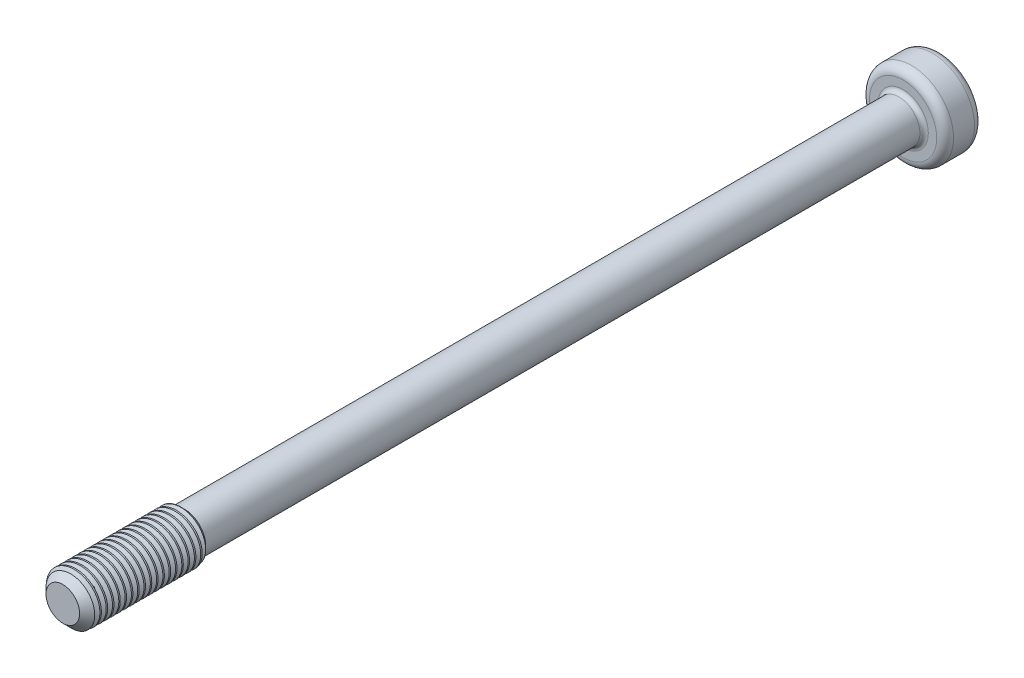
SolidWorks part; units mm, degrees
material "Plain Carbon Steel"
ref_plane "Front Plane" through (0, 0, 0) normal (0, 0, 1) x (1, 0, 0)
ref_plane "Top Plane" through (0, 0, 0) normal (0, 1, 0) x (1, 0, 0)
ref_plane "Right Plane" through (0, 0, 0) normal (1, 0, 0) x (0, 0, -1)
sketch "Sketch1" plane through (0, 0, 0) normal (0, 0, 1) x (1, 0, 0)
  circle A0 centre (0, 0) radius 1
  dimension "D1" = 2
extrude "Boss-Extrude1" add sketch "Sketch1" along normal blind 0.9
sketch "Sketch2" plane through (0, 0, 0.9) normal (0, 0, 1) x (1, 0, 0)
  circle A0 centre (0, 0) radius 0.5
  dimension "D1" = 1
extrude "Boss-Extrude2" add sketch "Sketch2" along normal blind 20
sketch "Sketch4" plane through (0, 0, 0) normal (0, 1, 0) x (1, 0, 0)
  line L0 (-1, -0.9) -> (1, -0.9) construction
  line L1 (-1, -0.9) -> (1, -0.9) construction
  line L2 (1, 0) -> (-1, 0) construction
  line L3 (0, -0.8) -> (0, 0)
  line L4 (1, 0) -> (-1, 0) construction
  line L6 (-0.75, 0) -> (-0.6089, -0.8)
  line L7 (-0.6089, -0.8) -> (0, -0.8)
  line L10 (-0.75, 0) -> (0, 0)
  point P6 (0.0056, -0.8)
  dimension "D1" = 0.25
  dimension "D2" = 0.1
  dimension "D4" = 100
ref_axis "Axis1" through (0, 0, 23.484) along (0, 0, -1)
extrude "Cut-Extrude5" cut sketch "Sketch4" against normal mid plane 0.3 contours L7 L10 L6 | L10 region at (-0.341, 0, 0.3862)
pattern_circular "CirPattern2" count 4 over 360 about axis through (0, 0, 23.484) along (0, 0, -1) of "Cut-Extrude5"
ref_plane "Plane1" through (0, 0, 0) normal (-0.7071, -0.7071, 0) x (0, 0, 1)
sketch "Sketch7" plane through (0, 0, 0) normal (-0.7071, -0.7071, 0) x (0, 0, 1)
  line L0 (0.8, 0.2121) -> (0, 0.2121) construction
  line L1 (0.8, 0.2121) -> (0, 0.2121) construction
  line L2 (0.9, -1) -> (0.9, 1) construction
  line L3 (23.484, 0) -> (-3.7079, 0) construction
  line L4 (0.8, 0) -> (0.9, 0)
  line L5 (0.9, 0) -> (0.8, 0.2121)
  line L6 (0.8, 0.2121) -> (0, 0.3)
  line L7 (0, 0.3) -> (0, 0)
  line L8 (0.8, 0) -> (0, 0)
  point P9 (0.7668, 0.2121)
  point P11 (0.738, 0.2121)
  point P12 (0, 0)
  point P13 (0, 0)
  point P14 (0, 0)
  point P15 (0, 0)
  point P18 (0, 0)
  dimension "D1" = 0.1
  dimension "D2" = 0.3
revolve "Cut-Revolve3" cut sketch "Sketch7" angle 360 about axis through (0, 0, 23.484) along (0, 0, -1) region at (-0.0735, 0.0735, 0.4255) region at (-0.1707, 0.1707, 0.2667)
fillet "Fillet2" radius 0.1 1 edges at (0.5, 0, 0.9)
fillet "Fillet3" radius 0.2 2 edges at (1, 0, 0) (1, 0, 0.9)
sketch "Sketch10" plane through (0, 0, 20.9) normal (0, 0, 1) x (1, 0, 0)
  circle A0 centre (0, 0) radius 0.6
  dimension "D1" = 1.2
extrude "Boss-Extrude3" add sketch "Sketch10" against normal blind 3
sketch "Sketch11" plane through (0, 0, 20.9) normal (0, 0, 1) x (1, 0, 0)
  circle A0 centre (0, 0) radius 0.5
  dimension "D1" = 1
curve "Helix/Spiral1" pitch 0.15 height 3.3 radius 0.5 centre (0, 0, 20.9) axis (0, 0, -1) start towards (-1, 0, 0)
chamfer "Chamfer1" distance 0.2 angle 45 2 edges at (0.6, 0, 17.9) (0.6, 0, 20.9)
sketch "Sketch13" plane through (0, 0, 0) normal (0, 1, 0) x (1, 0, 0)
  line L0 (-0.6, -18.1) -> (-0.6, -20.7) construction
  line L1 (-0.5, -20.9) -> (-0.6, -20.8423)
  line L2 (-0.6, -20.8423) -> (-0.6, -20.9577)
  line L3 (-0.6, -20.9577) -> (-0.5, -20.9)
  circle A0 centre (-0.5667, -20.9) radius 0.0333 construction
  spline S0 degree 3 poles (1998.2921, 45.2929) (154.1519, -21.7374) (-4.718, -21.2479) (-0.3628, -20.8813) (-0.1963, -20.8719) (0, -20.8625) (0.1963, -20.8531) (0.3628, -20.8438) (0.474, -20.8344) (0.513, -20.825) (0.474, -20.8156) (0.3628, -20.8063) (0.1963, -20.7969) (0, -20.7875) (-0.1963, -20.7781) (-0.3628, -20.7688) (-0.474, -20.7594) (-0.513, -20.75) (-0.474, -20.7406) (-0.3628, -20.7313) (-0.1963, -20.7219) (0, -20.7125) (0.1963, -20.7031) (0.3628, -20.6938) (0.474, -20.6844) (0.513, -20.675) (0.474, -20.6656) (0.3628, -20.6562) (0.1963, -20.6469) (0, -20.6375) (-0.1963, -20.6281) (-0.3628, -20.6187) (-0.474, -20.6094) (-0.513, -20.6) (-0.474, -20.5906) (-0.3628, -20.5813) (-0.1963, -20.5719) (0, -20.5625) (0.1963, -20.5531) (0.3628, -20.5437) (0.474, -20.5344) (0.513, -20.525) (0.474, -20.5156) (0.3628, -20.5063) (0.1963, -20.4969) (0, -20.4875) (-0.1963, -20.4781) (-0.3628, -20.4687) (-0.474, -20.4594) (-0.513, -20.45) (-0.474, -20.4406) (-0.3628, -20.4313) (-0.1963, -20.4219) (0, -20.4125) (0.1963, -20.4031) (0.3628, -20.3938) (0.474, -20.3844) (0.513, -20.375) (0.474, -20.3656) (0.3628, -20.3562) (0.1963, -20.3469) (0, -20.3375) (-0.1963, -20.3281) (-0.3628, -20.3188) (-0.474, -20.3094) (-0.513, -20.3) (-0.474, -20.2906) (-0.3628, -20.2812) (-0.1963, -20.2719) (0, -20.2625) (0.1963, -20.2531) (0.3628, -20.2438) (0.474, -20.2344) (0.513, -20.225) (0.474, -20.2156) (0.3628, -20.2063) (0.1963, -20.1969) (0, -20.1875) (-0.1963, -20.1781) (-0.3628, -20.1687) (-0.474, -20.1594) (-0.513, -20.15) (-0.474, -20.1406) (-0.3628, -20.1313) (-0.1963, -20.1219) (0, -20.1125) (0.1963, -20.1031) (0.3628, -20.0938) (0.474, -20.0844) (0.513, -20.075) (0.474, -20.0656) (0.3628, -20.0563) (0.1963, -20.0469) (0, -20.0375) (-0.1963, -20.0281) (-0.3628, -20.0187) (-0.474, -20.0094) (-0.513, -20) (-0.474, -19.9906) (-0.3628, -19.9812) (-0.1963, -19.9719) (0, -19.9625) (0.1963, -19.9531) (0.3628, -19.9437) (0.474, -19.9344) (0.513, -19.925) (0.474, -19.9156) (0.3628, -19.9063) (0.1963, -19.8969) (0, -19.8875) (-0.1963, -19.8781) (-0.3628, -19.8687) (-0.474, -19.8594) (-0.513, -19.85) (-0.474, -19.8406) (-0.3628, -19.8312) (-0.1963, -19.8219) (0, -19.8125) (0.1963, -19.8031) (0.3628, -19.7937) (0.474, -19.7844) (0.513, -19.775) (0.474, -19.7656) (0.3628, -19.7562) (0.1963, -19.7469) (0, -19.7375) (-0.1963, -19.7281) (-0.3628, -19.7187) (-0.474, -19.7094) (-0.513, -19.7) (-0.474, -19.6906) (-0.3628, -19.6812) (-0.1963, -19.6719) (0, -19.6625) (0.1963, -19.6531) (0.3628, -19.6437) (0.474, -19.6344) (0.513, -19.625) (0.474, -19.6156) (0.3628, -19.6062) (0.1963, -19.5969) (0, -19.5875) (-0.1963, -19.5781) (-0.3628, -19.5687) (-0.474, -19.5594) (-0.513, -19.55) (-0.474, -19.5406) (-0.3628, -19.5312) (-0.1963, -19.5219) (0, -19.5125) (0.1963, -19.5031) (0.3628, -19.4938) (0.474, -19.4844) (0.513, -19.475) (0.474, -19.4656) (0.3628, -19.4562) (0.1963, -19.4469) (0, -19.4375) (-0.1963, -19.4281) (-0.3628, -19.4187) (-0.474, -19.4094) (-0.513, -19.4) (-0.474, -19.3906) (-0.3628, -19.3812) (-0.1963, -19.3719) (0, -19.3625) (0.1963, -19.3531) (0.3628, -19.3437) (0.474, -19.3344) (0.513, -19.325) (0.474, -19.3156) (0.3628, -19.3063) (0.1963, -19.2969) (0, -19.2875) (-0.1963, -19.2781) (-0.3628, -19.2687) (-0.474, -19.2594) (-0.513, -19.25) (-0.474, -19.2406) (-0.3628, -19.2312) (-0.1963, -19.2219) (0, -19.2125) (0.1963, -19.2031) (0.3628, -19.1937) (0.474, -19.1844) (0.513, -19.175) (0.474, -19.1656) (0.3628, -19.1562) (0.1963, -19.1469) (0, -19.1375) (-0.1963, -19.1281) (-0.3628, -19.1187) (-0.474, -19.1094) (-0.513, -19.1) (-0.474, -19.0906) (-0.3628, -19.0812) (-0.1963, -19.0719) (0, -19.0625) (0.1963, -19.0531) (0.3628, -19.0437) (0.474, -19.0344) (0.513, -19.025) (0.474, -19.0156) (0.3628, -19.0062) (0.1963, -18.9969) (0, -18.9875) (-0.1963, -18.9781) (-0.3628, -18.9687) (-0.474, -18.9594) (-0.513, -18.95) (-0.474, -18.9406) (-0.3628, -18.9312) (-0.1963, -18.9219) (0, -18.9125) (0.1963, -18.9031) (0.3628, -18.8937) (0.474, -18.8844) (0.513, -18.875) (0.474, -18.8656) (0.3628, -18.8562) (0.1963, -18.8469) (0, -18.8375) (-0.1963, -18.8281) (-0.3628, -18.8187) (-0.474, -18.8094) (-0.513, -18.8) (-0.474, -18.7906) (-0.3628, -18.7812) (-0.1963, -18.7719) (0, -18.7625) (0.1963, -18.7531) (0.3628, -18.7437) (0.474, -18.7344) (0.513, -18.725) (0.474, -18.7156) (0.3628, -18.7062) (0.1963, -18.6969) (0, -18.6875) (-0.1963, -18.6781) (-0.3628, -18.6687) (-0.474, -18.6594) (-0.513, -18.65) (-0.474, -18.6406) (-0.3628, -18.6312) (-0.1963, -18.6219) (0, -18.6125) (0.1963, -18.6031) (0.3628, -18.5938) (0.474, -18.5844) (0.513, -18.575) (0.474, -18.5656) (0.3628, -18.5562) (0.1963, -18.5469) (0, -18.5375) (-0.1963, -18.5281) (-0.3628, -18.5188) (-0.474, -18.5094) (-0.513, -18.5) (-0.474, -18.4906) (-0.3628, -18.4813) (-0.1963, -18.4719) (0, -18.4625) (0.1963, -18.4531) (0.3628, -18.4438) (0.474, -18.4344) (0.513, -18.425) (0.474, -18.4156) (0.3628, -18.4063) (0.1963, -18.3969) (0, -18.3875) (-0.1963, -18.3781) (-0.3628, -18.3688) (-0.474, -18.3594) (-0.513, -18.35) (-0.474, -18.3406) (-0.3628, -18.3313) (-0.1963, -18.3219) (0, -18.3125) (0.1963, -18.3031) (0.3628, -18.2938) (0.474, -18.2844) (0.513, -18.275) (0.474, -18.2656) (0.3628, -18.2563) (0.1963, -18.2469) (0, -18.2375) (-0.1963, -18.2281) (-0.3628, -18.2188) (-0.474, -18.2094) (-0.513, -18.2) (-0.474, -18.1906) (-0.3628, -18.1813) (-0.1963, -18.1719) (0, -18.1625) (0.1963, -18.1531) (0.3628, -18.1438) (0.474, -18.1344) (0.513, -18.125) (0.474, -18.1156) (0.3628, -18.1063) (0.1963, -18.0969) (0, -18.0875) (-0.1963, -18.0781) (-0.3628, -18.0688) (-0.474, -18.0594) (-0.513, -18.05) (-0.474, -18.0406) (-0.3628, -18.0313) (-0.1963, -18.0219) (0, -18.0125) (0.1963, -18.0031) (0.3628, -17.9938) (0.474, -17.9844) (0.513, -17.975) (0.474, -17.9656) (0.3628, -17.9563) (0.1963, -17.9469) (0, -17.9375) (-0.1963, -17.9281) (-0.3628, -17.9188) (-0.474, -17.9094) (-0.513, -17.9) (-0.474, -17.8906) (-0.3628, -17.8813) (-0.1963, -17.8719) (0, -17.8625) (0.1963, -17.8531) (0.3628, -17.8438) (0.474, -17.8344) (0.513, -17.825) (0.474, -17.8156) (0.3628, -17.8063) (0.1963, -17.7969) (0, -17.7875) (-0.1963, -17.7781) (-0.3628, -17.7688) (-0.474, -17.7594) (-0.513, -17.75) (-0.474, -17.7406) (-0.3628, -17.7312) (-0.1963, -17.7219) (0, -17.7125) (0.1963, -17.7031) (0.3628, -17.6937) (0.474, -17.6844) (0.513, -17.675) (0.474, -17.6656) (0.3628, -17.6562) (0.1963, -17.6469) (0, -17.6375) (-0.1963, -17.6281) (-0.3628, -17.6187) (-4.7179, -17.2521) (154.1475, -16.7626) (1998.2156, -83.7902) knots -0.325249 -0.325249 -0.325249 -0.325249 0.002841 0.005682 0.008523 0.011364 0.014205 0.017045 0.019886 0.022727 0.025568 0.028409 0.03125 0.034091 0.036932 0.039773 0.042614 0.045455 0.048295 0.051136 0.053977 0.056818 0.059659 0.0625 0.065341 0.068182 0.071023 0.073864 0.076705 0.079545 0.082386 0.085227 0.088068 0.090909 0.09375 0.096591 0.099432 0.102273 0.105114 0.107955 0.110795 0.113636 0.116477 0.119318 0.122159 0.125 0.127841 0.130682 0.133523 0.136364 0.139205 0.142045 0.144886 0.147727 0.150568 0.153409 0.15625 0.159091 0.161932 0.164773 0.167614 0.170455 0.173295 0.176136 0.178977 0.181818 0.184659 0.1875 0.190341 0.193182 0.196023 0.198864 0.201705 0.204545 0.207386 0.210227 0.213068 0.215909 0.21875 0.221591 0.224432 0.227273 0.230114 0.232955 0.235795 0.238636 0.241477 0.244318 0.247159 0.25 0.252841 0.255682 0.258523 0.261364 0.264205 0.267045 0.269886 0.272727 0.275568 0.278409 0.28125 0.284091 0.286932 0.289773 0.292614 0.295455 0.298295 0.301136 0.303977 0.306818 0.309659 0.3125 0.315341 0.318182 0.321023 0.323864 0.326705 0.329545 0.332386 0.335227 0.338068 0.340909 0.34375 0.346591 0.349432 0.352273 0.355114 0.357955 0.360795 0.363636 0.366477 0.369318 0.372159 0.375 0.377841 0.380682 0.383523 0.386364 0.389205 0.392045 0.394886 0.397727 0.400568 0.403409 0.40625 0.409091 0.411932 0.414773 0.417614 0.420455 0.423295 0.426136 0.428977 0.431818 0.434659 0.4375 0.440341 0.443182 0.446023 0.448864 0.451705 0.454545 0.457386 0.460227 0.463068 0.465909 0.46875 0.471591 0.474432 0.477273 0.480114 0.482955 0.485795 0.488636 0.491477 0.494318 0.497159 0.5 0.502841 0.505682 0.508523 0.511364 0.514205 0.517045 0.519886 0.522727 0.525568 0.528409 0.53125 0.534091 0.536932 0.539773 0.542614 0.545455 0.548295 0.551136 0.553977 0.556818 0.559659 0.5625 0.565341 0.568182 0.571023 0.573864 0.576705 0.579545 0.582386 0.585227 0.588068 0.590909 0.59375 0.596591 0.599432 0.602273 0.605114 0.607955 0.610795 0.613636 0.616477 0.619318 0.622159 0.625 0.627841 0.630682 0.633523 0.636364 0.639205 0.642045 0.644886 0.647727 0.650568 0.653409 0.65625 0.659091 0.661932 0.664773 0.667614 0.670455 0.673295 0.676136 0.678977 0.681818 0.684659 0.6875 0.690341 0.693182 0.696023 0.698864 0.701705 0.704545 0.707386 0.710227 0.713068 0.715909 0.71875 0.721591 0.724432 0.727273 0.730114 0.732955 0.735795 0.738636 0.741477 0.744318 0.747159 0.75 0.752841 0.755682 0.758523 0.761364 0.764205 0.767045 0.769886 0.772727 0.775568 0.778409 0.78125 0.784091 0.786932 0.789773 0.792614 0.795455 0.798295 0.801136 0.803977 0.806818 0.809659 0.8125 0.815341 0.818182 0.821023 0.823864 0.826705 0.829545 0.832386 0.835227 0.838068 0.840909 0.84375 0.846591 0.849432 0.852273 0.855114 0.857955 0.860795 0.863636 0.866477 0.869318 0.872159 0.875 0.877841 0.880682 0.883523 0.886364 0.889205 0.892045 0.894886 0.897727 0.900568 0.903409 0.90625 0.909091 0.911932 0.914773 0.917614 0.920455 0.923295 0.926136 0.928977 0.931818 0.934659 0.9375 0.940341 0.943182 0.946023 0.948864 0.951705 0.954545 0.957386 0.960227 0.963068 0.965909 0.96875 0.971591 0.974432 0.977273 0.980114 0.982955 0.985795 0.988636 0.991477 0.994318 0.997159 1.325245 1.325245 1.325245 1.325245 only from (-0.5, -20.9) to (-0.5, -17.6) construction
  spline S1 degree 3 poles (-0.5, -20.9) (-0.5, -20.8969) (-0.474, -20.8906) (-0.3628, -20.8813) (-0.1963, -20.8719) (0, -20.8625) (0.1963, -20.8531) (0.3628, -20.8438) (0.474, -20.8344) (0.513, -20.825) (0.474, -20.8156) (0.3628, -20.8063) (0.1963, -20.7969) (0, -20.7875) (-0.1963, -20.7781) (-0.3628, -20.7688) (-0.474, -20.7594) (-0.513, -20.75) (-0.474, -20.7406) (-0.3628, -20.7313) (-0.1963, -20.7219) (0, -20.7125) (0.1963, -20.7031) (0.3628, -20.6938) (0.474, -20.6844) (0.513, -20.675) (0.474, -20.6656) (0.3628, -20.6562) (0.1963, -20.6469) (0, -20.6375) (-0.1963, -20.6281) (-0.3628, -20.6187) (-0.474, -20.6094) (-0.513, -20.6) (-0.474, -20.5906) (-0.3628, -20.5813) (-0.1963, -20.5719) (0, -20.5625) (0.1963, -20.5531) (0.3628, -20.5437) (0.474, -20.5344) (0.513, -20.525) (0.474, -20.5156) (0.3628, -20.5063) (0.1963, -20.4969) (0, -20.4875) (-0.1963, -20.4781) (-0.3628, -20.4687) (-0.474, -20.4594) (-0.513, -20.45) (-0.474, -20.4406) (-0.3628, -20.4313) (-0.1963, -20.4219) (0, -20.4125) (0.1963, -20.4031) (0.3628, -20.3938) (0.474, -20.3844) (0.513, -20.375) (0.474, -20.3656) (0.3628, -20.3562) (0.1963, -20.3469) (0, -20.3375) (-0.1963, -20.3281) (-0.3628, -20.3188) (-0.474, -20.3094) (-0.513, -20.3) (-0.474, -20.2906) (-0.3628, -20.2812) (-0.1963, -20.2719) (0, -20.2625) (0.1963, -20.2531) (0.3628, -20.2438) (0.474, -20.2344) (0.513, -20.225) (0.474, -20.2156) (0.3628, -20.2063) (0.1963, -20.1969) (0, -20.1875) (-0.1963, -20.1781) (-0.3628, -20.1687) (-0.474, -20.1594) (-0.513, -20.15) (-0.474, -20.1406) (-0.3628, -20.1313) (-0.1963, -20.1219) (0, -20.1125) (0.1963, -20.1031) (0.3628, -20.0938) (0.474, -20.0844) (0.513, -20.075) (0.474, -20.0656) (0.3628, -20.0563) (0.1963, -20.0469) (0, -20.0375) (-0.1963, -20.0281) (-0.3628, -20.0187) (-0.474, -20.0094) (-0.513, -20) (-0.474, -19.9906) (-0.3628, -19.9812) (-0.1963, -19.9719) (0, -19.9625) (0.1963, -19.9531) (0.3628, -19.9437) (0.474, -19.9344) (0.513, -19.925) (0.474, -19.9156) (0.3628, -19.9063) (0.1963, -19.8969) (0, -19.8875) (-0.1963, -19.8781) (-0.3628, -19.8687) (-0.474, -19.8594) (-0.513, -19.85) (-0.474, -19.8406) (-0.3628, -19.8312) (-0.1963, -19.8219) (0, -19.8125) (0.1963, -19.8031) (0.3628, -19.7937) (0.474, -19.7844) (0.513, -19.775) (0.474, -19.7656) (0.3628, -19.7562) (0.1963, -19.7469) (0, -19.7375) (-0.1963, -19.7281) (-0.3628, -19.7187) (-0.474, -19.7094) (-0.513, -19.7) (-0.474, -19.6906) (-0.3628, -19.6812) (-0.1963, -19.6719) (0, -19.6625) (0.1963, -19.6531) (0.3628, -19.6437) (0.474, -19.6344) (0.513, -19.625) (0.474, -19.6156) (0.3628, -19.6062) (0.1963, -19.5969) (0, -19.5875) (-0.1963, -19.5781) (-0.3628, -19.5687) (-0.474, -19.5594) (-0.513, -19.55) (-0.474, -19.5406) (-0.3628, -19.5312) (-0.1963, -19.5219) (0, -19.5125) (0.1963, -19.5031) (0.3628, -19.4938) (0.474, -19.4844) (0.513, -19.475) (0.474, -19.4656) (0.3628, -19.4562) (0.1963, -19.4469) (0, -19.4375) (-0.1963, -19.4281) (-0.3628, -19.4187) (-0.474, -19.4094) (-0.513, -19.4) (-0.474, -19.3906) (-0.3628, -19.3812) (-0.1963, -19.3719) (0, -19.3625) (0.1963, -19.3531) (0.3628, -19.3437) (0.474, -19.3344) (0.513, -19.325) (0.474, -19.3156) (0.3628, -19.3063) (0.1963, -19.2969) (0, -19.2875) (-0.1963, -19.2781) (-0.3628, -19.2687) (-0.474, -19.2594) (-0.513, -19.25) (-0.474, -19.2406) (-0.3628, -19.2312) (-0.1963, -19.2219) (0, -19.2125) (0.1963, -19.2031) (0.3628, -19.1937) (0.474, -19.1844) (0.513, -19.175) (0.474, -19.1656) (0.3628, -19.1562) (0.1963, -19.1469) (0, -19.1375) (-0.1963, -19.1281) (-0.3628, -19.1187) (-0.474, -19.1094) (-0.513, -19.1) (-0.474, -19.0906) (-0.3628, -19.0812) (-0.1963, -19.0719) (0, -19.0625) (0.1963, -19.0531) (0.3628, -19.0437) (0.474, -19.0344) (0.513, -19.025) (0.474, -19.0156) (0.3628, -19.0062) (0.1963, -18.9969) (0, -18.9875) (-0.1963, -18.9781) (-0.3628, -18.9687) (-0.474, -18.9594) (-0.513, -18.95) (-0.474, -18.9406) (-0.3628, -18.9312) (-0.1963, -18.9219) (0, -18.9125) (0.1963, -18.9031) (0.3628, -18.8937) (0.474, -18.8844) (0.513, -18.875) (0.474, -18.8656) (0.3628, -18.8562) (0.1963, -18.8469) (0, -18.8375) (-0.1963, -18.8281) (-0.3628, -18.8187) (-0.474, -18.8094) (-0.513, -18.8) (-0.474, -18.7906) (-0.3628, -18.7812) (-0.1963, -18.7719) (0, -18.7625) (0.1963, -18.7531) (0.3628, -18.7437) (0.474, -18.7344) (0.513, -18.725) (0.474, -18.7156) (0.3628, -18.7062) (0.1963, -18.6969) (0, -18.6875) (-0.1963, -18.6781) (-0.3628, -18.6687) (-0.474, -18.6594) (-0.513, -18.65) (-0.474, -18.6406) (-0.3628, -18.6312) (-0.1963, -18.6219) (0, -18.6125) (0.1963, -18.6031) (0.3628, -18.5938) (0.474, -18.5844) (0.513, -18.575) (0.474, -18.5656) (0.3628, -18.5562) (0.1963, -18.5469) (0, -18.5375) (-0.1963, -18.5281) (-0.3628, -18.5188) (-0.474, -18.5094) (-0.513, -18.5) (-0.474, -18.4906) (-0.3628, -18.4813) (-0.1963, -18.4719) (0, -18.4625) (0.1963, -18.4531) (0.3628, -18.4438) (0.474, -18.4344) (0.513, -18.425) (0.474, -18.4156) (0.3628, -18.4063) (0.1963, -18.3969) (0, -18.3875) (-0.1963, -18.3781) (-0.3628, -18.3688) (-0.474, -18.3594) (-0.513, -18.35) (-0.474, -18.3406) (-0.3628, -18.3313) (-0.1963, -18.3219) (0, -18.3125) (0.1963, -18.3031) (0.3628, -18.2938) (0.474, -18.2844) (0.513, -18.275) (0.474, -18.2656) (0.3628, -18.2563) (0.1963, -18.2469) (0, -18.2375) (-0.1963, -18.2281) (-0.3628, -18.2188) (-0.474, -18.2094) (-0.513, -18.2) (-0.474, -18.1906) (-0.3628, -18.1813) (-0.1963, -18.1719) (0, -18.1625) (0.1963, -18.1531) (0.3628, -18.1438) (0.474, -18.1344) (0.513, -18.125) (0.474, -18.1156) (0.3628, -18.1063) (0.1963, -18.0969) (0, -18.0875) (-0.1963, -18.0781) (-0.3628, -18.0688) (-0.474, -18.0594) (-0.513, -18.05) (-0.474, -18.0406) (-0.3628, -18.0313) (-0.1963, -18.0219) (0, -18.0125) (0.1963, -18.0031) (0.3628, -17.9938) (0.474, -17.9844) (0.513, -17.975) (0.474, -17.9656) (0.3628, -17.9563) (0.1963, -17.9469) (0, -17.9375) (-0.1963, -17.9281) (-0.3628, -17.9188) (-0.474, -17.9094) (-0.513, -17.9) (-0.474, -17.8906) (-0.3628, -17.8813) (-0.1963, -17.8719) (0, -17.8625) (0.1963, -17.8531) (0.3628, -17.8438) (0.474, -17.8344) (0.513, -17.825) (0.474, -17.8156) (0.3628, -17.8063) (0.1963, -17.7969) (0, -17.7875) (-0.1963, -17.7781) (-0.3628, -17.7688) (-0.474, -17.7594) (-0.513, -17.75) (-0.474, -17.7406) (-0.3628, -17.7312) (-0.1963, -17.7219) (0, -17.7125) (0.1963, -17.7031) (0.3628, -17.6937) (0.474, -17.6844) (0.513, -17.675) (0.474, -17.6656) (0.3628, -17.6562) (0.1963, -17.6469) (0, -17.6375) (-0.1963, -17.6281) (-0.3628, -17.6187) (-0.474, -17.6094) (-0.5, -17.6031) (-0.5, -17.6) knots 0 0 0 0 0.002841 0.005682 0.008523 0.011364 0.014205 0.017045 0.019886 0.022727 0.025568 0.028409 0.03125 0.034091 0.036932 0.039773 0.042614 0.045455 0.048295 0.051136 0.053977 0.056818 0.059659 0.0625 0.065341 0.068182 0.071023 0.073864 0.076705 0.079545 0.082386 0.085227 0.088068 0.090909 0.09375 0.096591 0.099432 0.102273 0.105114 0.107955 0.110795 0.113636 0.116477 0.119318 0.122159 0.125 0.127841 0.130682 0.133523 0.136364 0.139205 0.142045 0.144886 0.147727 0.150568 0.153409 0.15625 0.159091 0.161932 0.164773 0.167614 0.170455 0.173295 0.176136 0.178977 0.181818 0.184659 0.1875 0.190341 0.193182 0.196023 0.198864 0.201705 0.204545 0.207386 0.210227 0.213068 0.215909 0.21875 0.221591 0.224432 0.227273 0.230114 0.232955 0.235795 0.238636 0.241477 0.244318 0.247159 0.25 0.252841 0.255682 0.258523 0.261364 0.264205 0.267045 0.269886 0.272727 0.275568 0.278409 0.28125 0.284091 0.286932 0.289773 0.292614 0.295455 0.298295 0.301136 0.303977 0.306818 0.309659 0.3125 0.315341 0.318182 0.321023 0.323864 0.326705 0.329545 0.332386 0.335227 0.338068 0.340909 0.34375 0.346591 0.349432 0.352273 0.355114 0.357955 0.360795 0.363636 0.366477 0.369318 0.372159 0.375 0.377841 0.380682 0.383523 0.386364 0.389205 0.392045 0.394886 0.397727 0.400568 0.403409 0.40625 0.409091 0.411932 0.414773 0.417614 0.420455 0.423295 0.426136 0.428977 0.431818 0.434659 0.4375 0.440341 0.443182 0.446023 0.448864 0.451705 0.454545 0.457386 0.460227 0.463068 0.465909 0.46875 0.471591 0.474432 0.477273 0.480114 0.482955 0.485795 0.488636 0.491477 0.494318 0.497159 0.5 0.502841 0.505682 0.508523 0.511364 0.514205 0.517045 0.519886 0.522727 0.525568 0.528409 0.53125 0.534091 0.536932 0.539773 0.542614 0.545455 0.548295 0.551136 0.553977 0.556818 0.559659 0.5625 0.565341 0.568182 0.571023 0.573864 0.576705 0.579545 0.582386 0.585227 0.588068 0.590909 0.59375 0.596591 0.599432 0.602273 0.605114 0.607955 0.610795 0.613636 0.616477 0.619318 0.622159 0.625 0.627841 0.630682 0.633523 0.636364 0.639205 0.642045 0.644886 0.647727 0.650568 0.653409 0.65625 0.659091 0.661932 0.664773 0.667614 0.670455 0.673295 0.676136 0.678977 0.681818 0.684659 0.6875 0.690341 0.693182 0.696023 0.698864 0.701705 0.704545 0.707386 0.710227 0.713068 0.715909 0.71875 0.721591 0.724432 0.727273 0.730114 0.732955 0.735795 0.738636 0.741477 0.744318 0.747159 0.75 0.752841 0.755682 0.758523 0.761364 0.764205 0.767045 0.769886 0.772727 0.775568 0.778409 0.78125 0.784091 0.786932 0.789773 0.792614 0.795455 0.798295 0.801136 0.803977 0.806818 0.809659 0.8125 0.815341 0.818182 0.821023 0.823864 0.826705 0.829545 0.832386 0.835227 0.838068 0.840909 0.84375 0.846591 0.849432 0.852273 0.855114 0.857955 0.860795 0.863636 0.866477 0.869318 0.872159 0.875 0.877841 0.880682 0.883523 0.886364 0.889205 0.892045 0.894886 0.897727 0.900568 0.903409 0.90625 0.909091 0.911932 0.914773 0.917614 0.920455 0.923295 0.926136 0.928977 0.931818 0.934659 0.9375 0.940341 0.943182 0.946023 0.948864 0.951705 0.954545 0.957386 0.960227 0.963068 0.965909 0.96875 0.971591 0.974432 0.977273 0.980114 0.982955 0.985795 0.988636 0.991477 0.994318 0.997159 1 1 1 1 construction
  point P1 (-0.5774, -20.9144)
  point P6 (0, 0)
  point P7 (0, 0)
  point P10 (0, 0)
sweep "Cut-Sweep1" cut profiles "Sketch13" path "Helix/Spiral1" align with end faces yes
